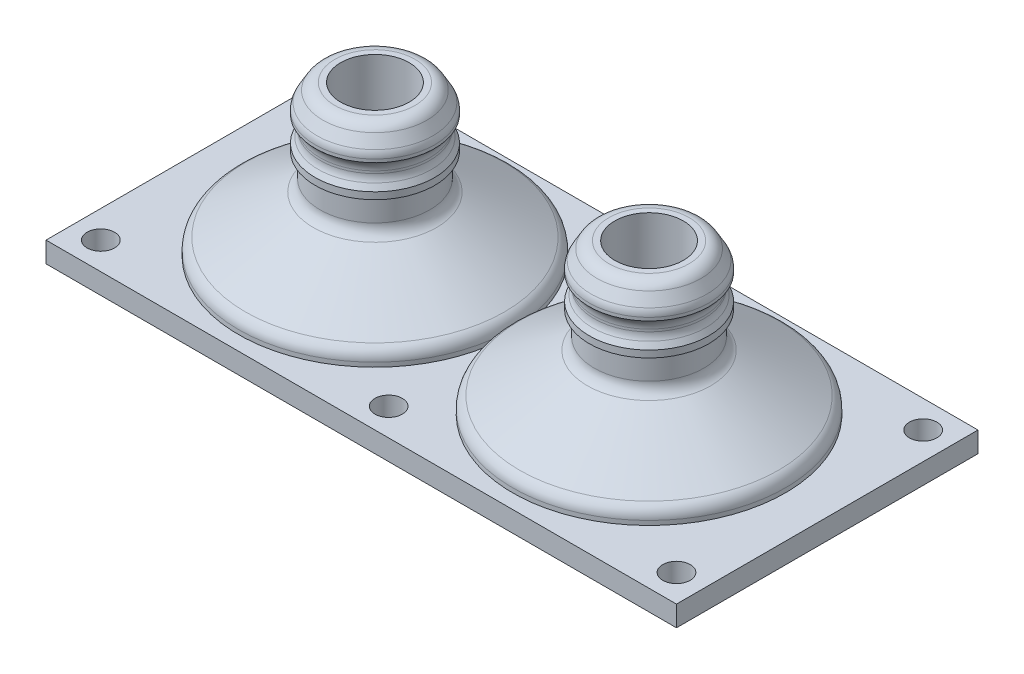
SolidWorks part; units mm, degrees
ref_plane "Front Plane" through (0, 0, 0) normal (0, 0, 1) x (1, 0, 0)
ref_plane "Top Plane" through (0, 0, 0) normal (0, 1, 0) x (1, 0, 0)
ref_plane "Right Plane" through (0, 0, 0) normal (1, 0, 0) x (0, 0, -1)
sketch "Sketch1" plane through (0, 0, 0) normal (0, 1, 0) x (1, 0, 0)
  line L0 (0, 0) -> (46, 0) construction
  line L1 (-46, -22) -> (46, -22)
  line L2 (-46, -22) -> (-46, 22)
  line L3 (-46, 22) -> (46, 22)
  line L4 (46, -22) -> (46, 22)
  line L5 (-46, -22) -> (46, 22) construction
  line L6 (-46, 22) -> (46, -22) construction
  line L7 (0, 0) -> (0, 22) construction
  line L8 (0, 18) -> (46, 18) construction
  circle A0 centre (-20, 0) radius 17
  circle A1 centre (20, 0) radius 17
  circle A2 centre (0, 18) radius 2
  circle A4 centre (-42, 18) radius 2
  circle A5 centre (-42, -18) radius 2
  circle A6 centre (42, 18) radius 2
  circle A7 centre (0, -18) radius 2
  circle A8 centre (42, -18) radius 2
  point P0 (0, 0)
  point P25 (40.4906, 0)
  point P27 (0, 0)
  dimension "D2" = 34
  dimension "D6" = 4
  dimension "D1" = 40
  dimension "D3" = 22
  dimension "D4" = 26
  dimension "D5" = 18
  dimension "D7" = 42
extrude "Boss-Extrude1" add sketch "Sketch1" along normal blind 3
sketch "Sketch2" plane through (0, 3, 0) normal (0, 1, 0) x (1, 0, 0)
  point P0 (-20, 0)
  point P1 (20, 0)
sketch3d "3DSketch3"
  line L0 (-20, 3, 0) -> (-20, 35.1077, 0) construction
  line L2 (-3, 3, 0) -> (-15, 9.9282, 0)
  line L3 (-15, 9.9282, 0) -> (-15, 24.9282, 0)
  line L4 (-15, 24.9282, 0) -> (-13, 24.9282, 0)
  line L6 (-13, 24.9282, 0) -> (-11.275, 21.9404, 0)
  line L7 (-11.275, 21.9404, 0) -> (-11.275, 20.9404, 0)
  line L8 (-11.275, 20.9404, 0) -> (-12, 20.5218, 0)
  line L9 (-12, 20.5218, 0) -> (-12, 18.5218, 0)
  line L11 (-12, 11.6603, 0) -> (-0.1, 4.7898, 0)
  line L12 (-0.1, 4.7898, 0) -> (-0.1, 3, 0)
  line L13 (-0.1, 3, 0) -> (-3, 3, 0)
  line L14 (-12, 18.5218, 0) -> (-11.275, 17.2661, 0)
  line L15 (-11.275, 17.2661, 0) -> (-11.275, 16.2661, 0)
  line L16 (-11.275, 16.2661, 0) -> (-12, 15.8475, 0)
  line L17 (-12, 15.8475, 0) -> (-12, 11.6603, 0)
  circle A1 centre (-20, 3, 0) radius 17 construction
  point P29 (-20, 20, 0)
  dimension "D1" = 17.45
  dimension "D2" = 16
  dimension "D3" = 10
  dimension "D4" = 3
  dimension "D5" = 2.9
  dimension "D6" = 120
  dimension "D7" = 1
  dimension "D8" = 150
  dimension "D9" = 2
  dimension "D10" = 2
  dimension "D11" = 150
  dimension "D12" = 15
revolve "Revolve1" add sketch "3DSketch3" angle 360 about L0
sketch3d "3DSketch5"
  line L21 (20, 3, 0) -> (20, 35.1077, 0) construction
  line L22 (37, 3, 0) -> (25, 9.9282, 0)
  line L23 (25, 9.9282, 0) -> (25, 24.9282, 0)
  line L24 (25, 24.9282, 0) -> (27, 24.9282, 0)
  line L25 (27, 24.9282, 0) -> (28.725, 21.9404, 0)
  line L26 (28.725, 21.9404, 0) -> (28.725, 20.9404, 0)
  line L27 (28.725, 20.9404, 0) -> (28, 20.5218, 0)
  line L28 (28, 20.5218, 0) -> (28, 18.5218, 0)
  line L29 (28, 11.6603, 0) -> (39.9, 4.7898, 0)
  line L30 (39.9, 4.7898, 0) -> (39.9, 3, 0)
  line L31 (39.9, 3, 0) -> (37, 3, 0)
  line L32 (28, 18.5218, 0) -> (28.725, 17.2661, 0)
  line L33 (28.725, 17.2661, 0) -> (28.725, 16.2661, 0)
  line L34 (28.725, 16.2661, 0) -> (28, 15.8475, 0)
  line L35 (28, 15.8475, 0) -> (28, 11.6603, 0)
  point P1 (18.0233, 34.1418, 0)
revolve "Revolve7" add sketch "3DSketch5" angle 360 about L21
fillet "Fillet11" radius 2 16 edges at (-20, 3, -17) (-20, 9.9282, -5) (37, 3, 0) (25, 9.9282, 0) (28, 20.5218, 0) (28, 18.5218, 0) (-20, 24.9282, -7) (-20, 21.9404, -8.725) (-20, 20.5218, -8) (-20, 18.5218, -8) (27, 24.9282, 0) (28.725, 21.9404, 0) (28, 11.6603, 0) (39.9, 4.7898, 0) (-20, 11.6603, -8) (-20, 4.7898, -19.9)
